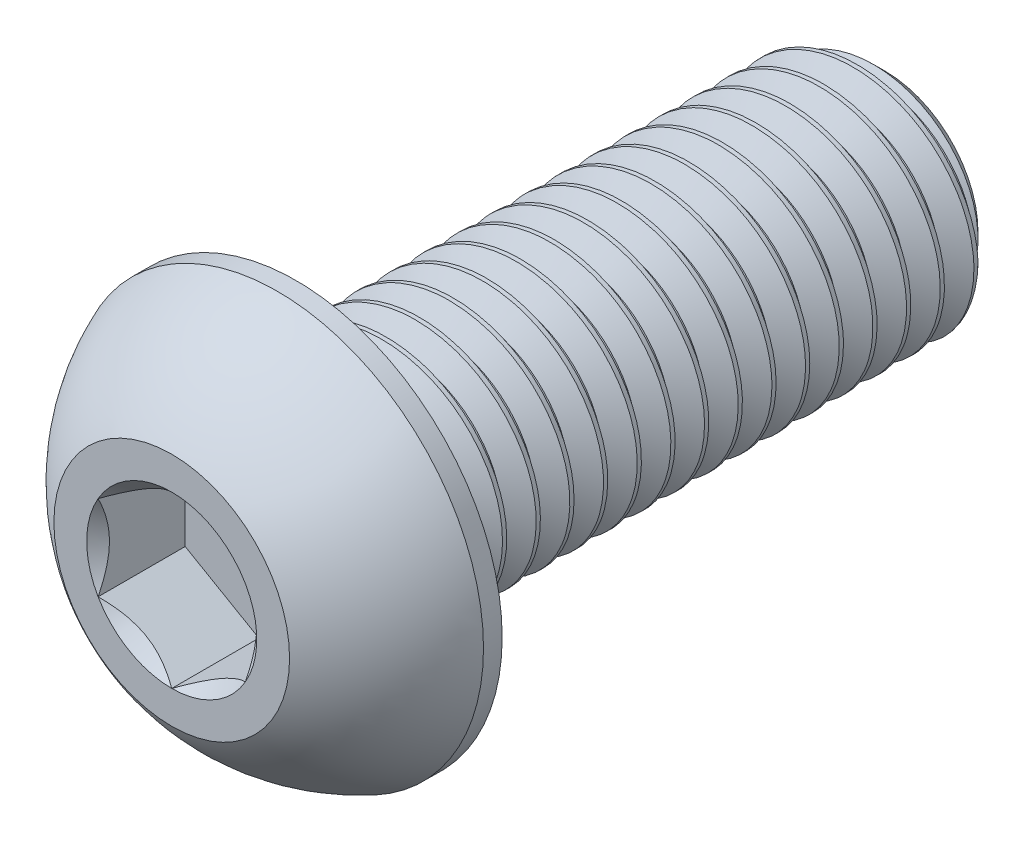
SolidWorks part; units mm, degrees
ref_plane "Front" through (0, 0, 0) normal (0, 0, 1) x (1, 0, 0)
ref_plane "Top" through (0, 0, 0) normal (0, 1, 0) x (1, 0, 0)
ref_plane "Right" through (0, 0, 0) normal (1, 0, 0) x (0, 0, -1)
sketch "Sketch1" plane through (0, 0, 0) normal (1, 0, 0) x (0, 0, -1)
  line L2 (3.3528, 3.175) -> (19.2278, 3.175)
  line L3 (19.2278, 3.175) -> (19.2278, 0)
  line L4 (19.2278, 0) -> (3.3528, 0)
  line L6 (2.8499, 5.5499) -> (3.3528, 5.5499) construction
  line L7 (19.2278, 3.175) -> (19.2278, -3.175) construction
  line L8 (0, 0) -> (3.3528, 0) construction
  line L9 (3.3528, 5.5499) -> (3.3528, -5.5499) construction
  line L11 (3.3528, 3.175) -> (3.3528, 0)
  line L13 (0, 1.9844) -> (0, -1.9844) construction
  line L14 (0, 1.9844) -> (0, 3.175) construction
  arc A3 (0, 3.175) -> (2.8499, 5.5499) centre (5.0603, 0) cw construction
  dimension "D1" = 0.5029
  dimension "Head Ht" = 3.3528
  dimension "Head Dia" = 11.0998
  dimension "Dia" = 6.35
  dimension "Lg" = 15.875
  dimension "Hex" = 3.9688
revolve "Revolve1" add sketch "Sketch1" angle 360 mid plane about L4
sketch "Sketch3" plane through (0, 0, -19.2278) normal (0, 0, -1) x (-1, 0, 0)
  circle A0 centre (0, 0) radius 3.175
curve "Helix/Spiral1" pitch 0.9071 height 16.7821 turns 18.5
sketch "Sketch2" plane through (0, 0, 0) normal (1, 0, 0) x (0, 0, -1)
  line L0 (19.2278, 3.175) -> (20.0215, 3.175)
  line L1 (20.0215, 3.175) -> (19.6814, 2.5858)
  line L2 (19.6814, 2.5858) -> (19.568, 2.5858)
  line L3 (19.568, 2.5858) -> (19.2278, 3.175)
  line L4 (19.3979, 2.8804) -> (19.8515, 2.8804) construction
  dimension "D1" = 60
  dimension "D2" = 0.1134
  dimension "D3" = 0.4536
chamfer "Chamfer1" distance 0.6804 angle 45 1 edges at (0, 3.175, -19.2278)
sweep "Cut-Sweep1" cut profiles "Sketch2" path "Helix/Spiral1" align with end faces yes
sketch "Sketch7" plane through (0, 0, 0) normal (1, 0, 0) x (0, 0, -1)
  line L6 (2.8499, 5.5499) -> (3.3528, 5.5499) construction
  line L8 (0, 0) -> (3.3528, 0) construction
  line L11 (3.3528, 5.5499) -> (3.3528, -5.5499) construction
  line L12 (2.8499, 5.5499) -> (3.3528, 5.5499)
  line L13 (0, 0) -> (3.3528, 0)
  line L14 (0, 1.9844) -> (0, -1.9844) construction
  line L15 (3.3528, 5.5499) -> (3.3528, 0)
  line L16 (0, 3.175) -> (0, 0)
  arc A2 (2.8499, 5.5499) -> (0, 3.175) centre (5.0603, 0) ccw construction
  arc A3 (2.8499, 5.5499) -> (0, 3.175) centre (5.0603, 0) ccw
revolve "Revolve2" add sketch "Sketch7" angle 360 mid plane about L13
sketch "Sketch5" plane through (0, 0, 0) normal (0, 0, 1) x (1, 0, 0)
  line L1 (1.9844, -1.1457) -> (1.9844, 1.1457)
  line L2 (1.9844, 1.1457) -> (0, 2.2914)
  line L3 (0, 2.2914) -> (-1.9844, 1.1457)
  line L4 (-1.9844, 1.1457) -> (-1.9844, -1.1457)
  line L5 (-1.9844, -1.1457) -> (0, -2.2914)
  line L6 (0, -2.2914) -> (1.9844, -1.1457)
  circle A0 centre (0, 0) radius 1.9844 construction
extrude "Cut-Extrude2" cut sketch "Sketch5" against normal blind 2.347
sketch "Sketch6" plane through (0, 0, 0) normal (0, 0, 1) x (1, 0, 0)
  circle A0 centre (0, 0) radius 2.2914
extrude "Cut-Extrude3" cut sketch "Sketch6" against normal blind 2.347 draft 45
sketch "Sketch9" [suppressed] plane through (0, 0, -3.3528) normal (0, 0, 1) x (1, 0, 0)
  circle A2 centre (0, 0) radius 3.175
extrude "Boss-Extrude2" [suppressed] add sketch "Sketch9" against normal offset from surface (25.4 mm away) 22.225
sketch "Sketch10" plane through (0, 0, 0) normal (1, 0, 0) x (0, 0, -1)
  line L0 (19.2278, 3.175) -> (19.2278, -3.175) construction
  point P0 (17.8671, -3.175)
  dimension "D1" = 1.3607
equation "\"D3@Helix/Spiral1\" = \"Lg@Sketch1\" + \"D4@Helix/Spiral1\""
equation "\"D2@Sketch2\" = \"D4@Helix/Spiral1\" * .125"
equation "\"D3@Sketch2\" = \"D4@Helix/Spiral1\" * .5"
equation "\"D1@Chamfer1\" = \"D4@Helix/Spiral1\" * .75"
equation "\"D1@Cut-Extrude2\" = \"Head Ht@Sketch1\" * .7"
equation "\"D1@Sketch1\" = \"Head Ht@Sketch1\" * .15"
equation "\"D1@Sketch10\" = \"D4@Helix/Spiral1\" * 1.5"
equation "\"D1@Cut-Extrude3\" = \"D1@Cut-Extrude2\""
